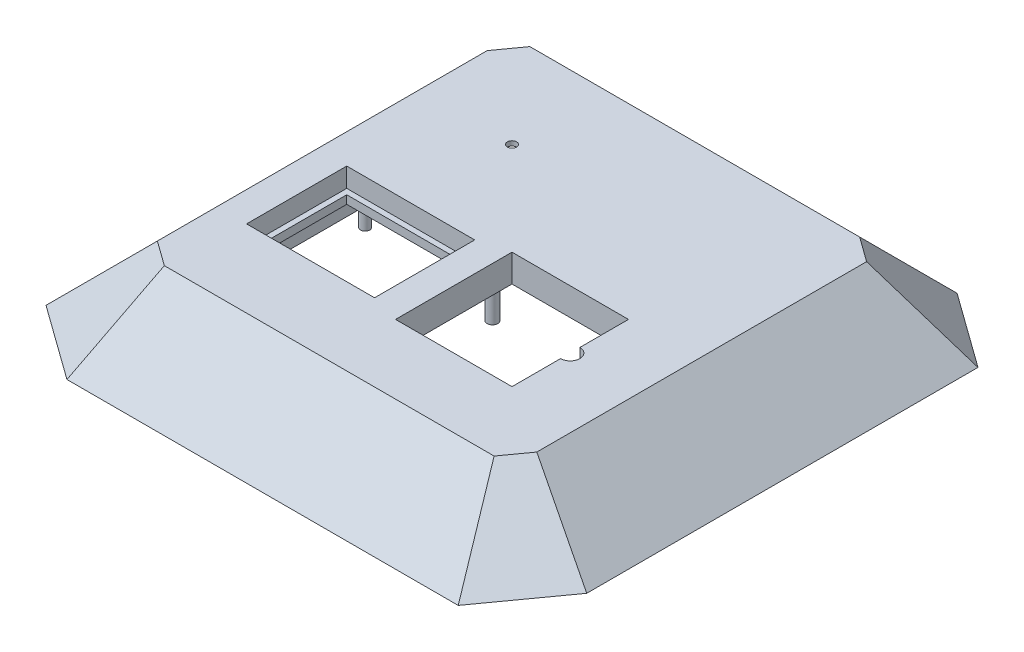
SolidWorks part; units mm, degrees
ref_plane "Front Plane" through (0, 0, 0) normal (0, 0, 1) x (1, 0, 0)
ref_plane "Top Plane" through (0, 0, 0) normal (0, 1, 0) x (1, 0, 0)
ref_plane "Right Plane" through (0, 0, 0) normal (1, 0, 0) x (0, 0, -1)
sketch "Sketch1" plane through (0, 0, 0) normal (0, 1, 0) x (1, 0, 0)
  line L0 (-47.3454, -21.7516) -> (37.6546, -21.7516)
  line L1 (37.6546, -21.7516) -> (49.3368, -5.5181)
  line L2 (49.3368, -5.5181) -> (49.3368, 79.4819)
  line L3 (49.3368, 79.4819) -> (33.1033, 91.1641)
  line L4 (33.1033, 91.1641) -> (-51.8967, 91.1641)
  line L5 (-51.8967, 91.1641) -> (-63.5789, 74.9306)
  line L6 (-63.5789, 74.9306) -> (-63.5789, -10.0694)
  line L7 (-63.5789, -10.0694) -> (-47.3454, -21.7516)
  dimension "D2" = 85
  dimension "D3" = 85
  dimension "D4" = 144.26
  dimension "D5" = 144.26
  dimension "D6" = 85
  dimension "D7" = 144.26
  dimension "D8" = 20
  dimension "D9" = 85
  dimension "D10" = 20
  dimension "D11" = 20
extrude "Boss-Extrude2" add sketch "Sketch1" along normal blind 16
sketch "Sketch4" plane through (0, 0, 0) normal (0, -1, 0) x (1, 0, 0)
  line L16 (-42.1868, 5.7516) -> (-47.5789, 1.8712)
  line L17 (-47.5789, 1.8712) -> (-47.5789, -69.772)
  line L18 (-47.5789, -69.772) -> (-43.6985, -75.1641)
  line L19 (-43.6985, -75.1641) -> (27.9447, -75.1641)
  line L20 (27.9447, -75.1641) -> (33.3368, -71.2838)
  line L21 (33.3368, -71.2838) -> (33.3368, 0.3594)
  line L22 (33.3368, 0.3594) -> (29.4564, 5.7516)
  line L23 (29.4564, 5.7516) -> (-42.1868, 5.7516)
  line L24 (-42.1868, 5.7516) -> (-47.5789, 1.8712)
  line L25 (-47.5789, 1.8712) -> (-47.5789, -69.772)
  line L26 (-47.5789, -69.772) -> (-43.6985, -75.1641)
  line L27 (-43.6985, -75.1641) -> (27.9447, -75.1641)
  line L28 (27.9447, -75.1641) -> (33.3368, -71.2838)
  line L29 (33.3368, -71.2838) -> (33.3368, 0.3594)
  line L30 (33.3368, 0.3594) -> (29.4564, 5.7516)
  line L31 (29.4564, 5.7516) -> (-42.1868, 5.7516)
  dimension "D1" = 16
chamfer "Chamfer1" distance 16 angle 45 8 edges at (-63.5789, 16, -32.4306) (-57.7378, 16, -83.0473) (-9.3967, 16, -91.1641) (41.22, 16, -85.323) (49.3368, 16, -36.9819) (43.4957, 16, 13.6348) (-4.8454, 16, 21.7516) (-55.4621, 16, 15.9105)
extrude "Cut-Extrude3" cut sketch "Sketch4" against normal blind 10
sketch "Sketch6" plane through (0, 16, 0) normal (0, 1, 0) x (1, 0, 0)
  line L0 (33.3368, -0.3594) -> (33.3368, 71.2838) construction
  line L1 (-6.9632, 34.5484) -> (18.3368, 34.5484)
  line L2 (-6.9632, 34.5484) -> (-6.9632, 9.2484)
  line L3 (-6.9632, 9.2484) -> (18.3368, 9.2484)
  line L4 (18.3368, 34.5484) -> (18.3368, 9.2484)
  line L5 (-42.1868, -5.7516) -> (29.4564, -5.7516) construction
  dimension "D1" = 25.3
  dimension "D2" = 25.3
  dimension "D3" = 15
  dimension "D4" = 15
extrude "Cut-Extrude4" cut sketch "Sketch6" against normal up to next
sketch "Sketch7" plane through (0, 10, 0) normal (0, -1, 0) x (1, 0, 0)
  line L0 (18.3368, -9.2484) -> (18.3368, -34.5484) construction
  circle A0 centre (18.3368, -21.8984) radius 2.0981
extrude "Cut-Extrude5" cut sketch "Sketch7" against normal up to next
sketch "Sketch8" plane through (0, 10, 0) normal (0, -1, 0) x (1, 0, 0)
  line L0 (-11.7632, -21.9984) -> (30.1662, -21.9984) construction
  line L1 (-11.7632, -8.8984) -> (24.2368, -8.8984)
  line L2 (-11.7632, -8.8984) -> (-11.7632, -35.0984)
  line L3 (-11.7632, -35.0984) -> (24.2368, -35.0984)
  line L4 (24.2368, -8.8984) -> (24.2368, -35.0984)
  line L5 (6.2368, -8.8984) -> (6.2368, -38.2867) construction
  line L6 (33.3368, -71.2838) -> (33.3368, 0.3594) construction
  line L7 (29.4564, 5.7516) -> (-42.1868, 5.7516) construction
  circle A0 centre (-9.2132, -11.4484) radius 1.15
  circle A1 centre (21.6868, -11.4484) radius 1.15
  circle A2 centre (21.6868, -32.5484) radius 1.15
  circle A3 centre (-9.2132, -32.5484) radius 1.15
  dimension "D3" = 2.3
  dimension "D4" = 2.55
  dimension "D5" = 2.55
  dimension "D6" = 9.1
  dimension "D1" = 36
  dimension "D2" = 26.2
  dimension "D7" = 14.65
extrude "Boss-Extrude3" add sketch "Sketch8" along normal blind 7 contours A0 | A1 | A2 | A3 region at (-9.2132, 10, -11.4484) region at (21.6868, 10, -11.4484) region at (21.6868, 10, -32.5484)
sketch "Sketch9" plane through (0, 10, 0) normal (0, -1, 0) x (1, 0, 0)
  line L2 (-47.5789, 1.8712) -> (-47.5789, -69.772) construction
  line L3 (-43.6985, -75.1641) -> (27.9447, -75.1641) construction
  circle A0 centre (-27.2189, -54.8041) radius 15.65
  dimension "D1" = 20.36
  dimension "D2" = 20.36
  dimension "D3" = 31.3
extrude "Cut-Extrude6" cut sketch "Sketch9" against normal blind 5
sketch "Sketch10" plane through (0, 15, 0) normal (0, -1, 0) x (1, 0, 0)
  circle A0 centre (-27.2189, -54.8041) radius 1
  dimension "D1" = 2
extrude "Cut-Extrude7" cut sketch "Sketch10" against normal up to next
sketch "Sketch11" plane through (0, 16, 0) normal (0, 1, 0) x (1, 0, 0)
  line L0 (-14.7144, 21.8984) -> (-6.9632, 21.8984) construction
  line L1 (-14.7144, 35.3984) -> (-39.7144, 35.3984)
  line L2 (-14.7144, 35.3984) -> (-14.7144, 8.3984)
  line L3 (-14.7144, 8.3984) -> (-39.7144, 8.3984)
  line L4 (-39.7144, 35.3984) -> (-39.7144, 8.3984)
  line L5 (-6.9632, 34.5484) -> (-6.9632, 9.2484) construction
  line L6 (-27.2144, 35.3984) -> (-27.2144, 2.0931) construction
  line L7 (-14.7144, 21.8984) -> (-44.3409, 21.8984) construction
  circle A0 centre (-37.5644, 33.2484) radius 1
  circle A1 centre (-16.8644, 33.2484) radius 1
  circle A2 centre (-16.8644, 10.5484) radius 1
  circle A3 centre (-37.5644, 10.5484) radius 1
  dimension "D3" = 2
  dimension "D4" = 2.15
  dimension "D5" = 2.15
  dimension "D1" = 25
  dimension "D2" = 27
extrude "Boss-Extrude4" add sketch "Sketch11" against normal blind 10 contours A0 | A1 | A2 | A3
sketch "Sketch12" plane through (0, 16, 0) normal (0, 1, 0) x (1, 0, 0)
  line L0 (-14.7144, 35.3984) -> (-14.7144, 8.3984) construction
  line L1 (-39.9144, 31.5984) -> (-14.5144, 31.5984)
  line L2 (-39.9144, 31.5984) -> (-39.9144, 12.2384)
  line L3 (-39.9144, 12.2384) -> (-14.5144, 12.2384)
  line L4 (-14.5144, 31.5984) -> (-14.5144, 12.2384)
  line L5 (-39.7144, 35.3984) -> (-39.7144, 8.3984) construction
  line L6 (-14.7144, 35.3984) -> (-39.7144, 35.3984) construction
  line L7 (-14.7144, 8.3984) -> (-39.7144, 8.3984) construction
  dimension "D1" = 0.2
  dimension "D2" = 0.2
  dimension "D3" = 3.8
  dimension "D4" = 3.84
extrude "Cut-Extrude8" cut sketch "Sketch12" against normal through all
sketch "Sketch13" plane through (0, 16, 0) normal (0, 1, 0) x (1, 0, 0)
  line L0 (-14.5144, 31.5984) -> (-39.9144, 31.5984) construction
  line L1 (-41.1144, 32.7984) -> (-13.3144, 32.7984)
  line L2 (-41.1144, 32.7984) -> (-41.1144, 11.0384)
  line L3 (-41.1144, 11.0384) -> (-13.3144, 11.0384)
  line L4 (-13.3144, 32.7984) -> (-13.3144, 11.0384)
  line L5 (-39.9144, 31.5984) -> (-39.9144, 12.2384) construction
  line L6 (-14.5144, 12.2384) -> (-14.5144, 31.5984) construction
  line L7 (-39.9144, 12.2384) -> (-14.5144, 12.2384) construction
  dimension "D1" = 1.2
  dimension "D2" = 1.2
  dimension "D3" = 1.2
  dimension "D4" = 1.2
extrude "Cut-Extrude9" cut sketch "Sketch13" against normal blind 4.2
